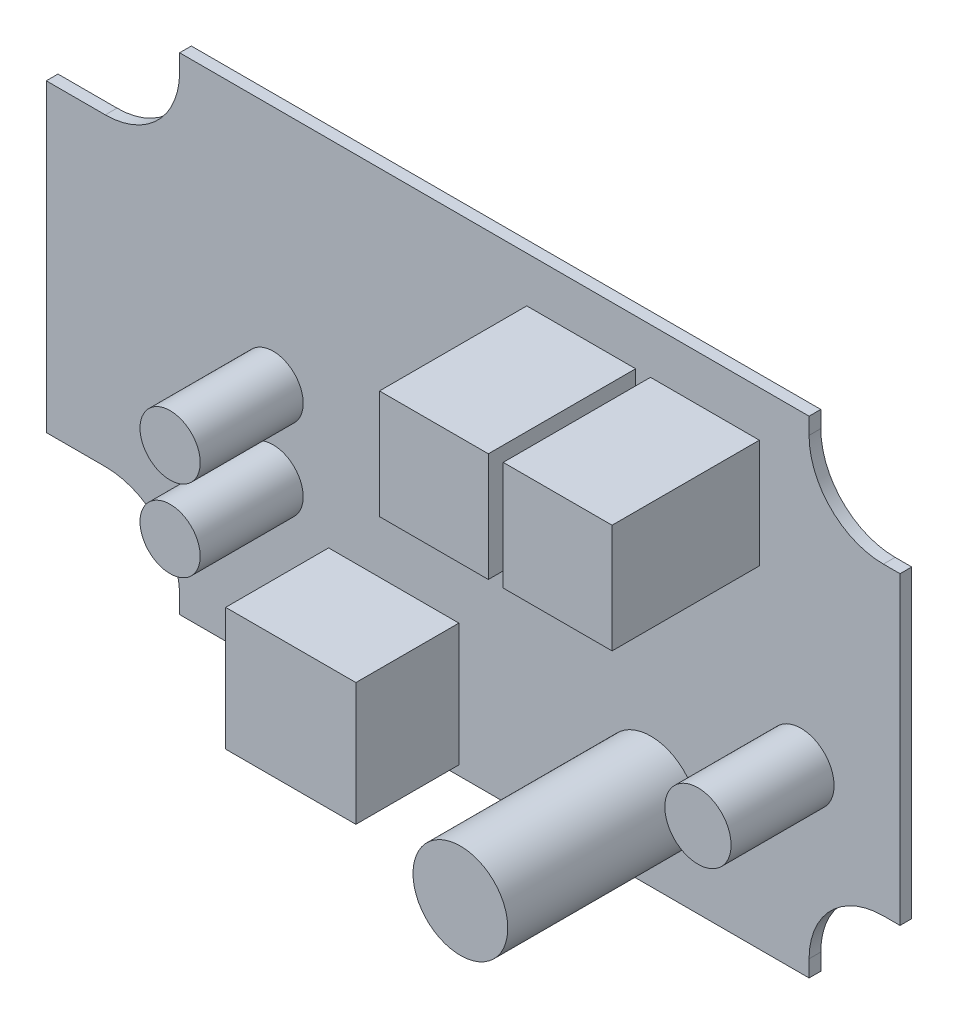
SolidWorks part; units mm, degrees
ref_plane "Front Plane" through (0, 0, 0) normal (0, 0, 1) x (1, 0, 0)
ref_plane "Top Plane" through (0, 0, 0) normal (0, 1, 0) x (1, 0, 0)
ref_plane "Right Plane" through (0, 0, 0) normal (1, 0, 0) x (0, 0, -1)
sketch "Sketch1" plane through (0, 0, 0) normal (0, 0, 1) x (1, 0, 0)
  line L0 (-42.3541, 30.2967) -> (-52.3541, 30.2967) construction
  line L1 (42.3541, -30.7033) -> (42.3541, -32.9433)
  line L2 (-52.3541, -20.7033) -> (-60.3013, -20.7033)
  line L4 (52.3541, -20.7033) -> (54.5933, -20.7033)
  line L5 (-52.3541, 30.2967) -> (-52.3541, 20.2967) construction
  line L6 (-52.3541, -20.7033) -> (-52.3541, -30.7033) construction
  line L7 (-52.3541, -30.7033) -> (-42.3541, -30.7033) construction
  line L8 (42.3541, -30.7033) -> (52.3541, -30.7033) construction
  line L9 (52.3541, -30.7033) -> (52.3541, -20.7033) construction
  line L10 (52.3541, 20.2967) -> (52.3541, 30.2967) construction
  line L11 (52.3541, 30.2967) -> (42.3541, 30.2967) construction
  line L12 (54.5933, -20.7033) -> (54.5933, 20.2967)
  line L13 (-60.3013, -20.7033) -> (-60.3013, 20.2967)
  line L14 (-60.3013, 20.2967) -> (-52.3541, 20.2967)
  line L15 (54.5933, 20.2967) -> (52.3541, 20.2967)
  line L16 (42.3541, -32.9433) -> (-42.3541, -32.9433)
  line L17 (-42.3541, -32.9433) -> (-42.3541, -30.7033)
  line L21 (0, -32.9433) -> (0, 0) construction
  line L24 (42.3541, 30.2967) -> (42.3541, 32.5367)
  line L25 (42.3541, 32.5367) -> (-42.3541, 32.5367)
  line L26 (-42.3541, 32.5367) -> (-42.3541, 30.2967)
  arc A0 (-42.3541, 30.2967) -> (-52.3541, 20.2967) centre (-52.3541, 30.2967) cw
  arc A2 (-52.3541, -20.7033) -> (-42.3541, -30.7033) centre (-52.3541, -30.7033) cw
  arc A4 (42.3541, 30.2967) -> (52.3541, 20.2967) centre (52.3541, 30.2967) ccw
  arc A5 (52.3541, -20.7033) -> (42.3541, -30.7033) centre (52.3541, -30.7033) ccw
  dimension "D1" = 41
  dimension "D3" = 10
  dimension "D5" = 84.7082
  dimension "D6" = 2.24
  dimension "D7" = 7.9472
  dimension "D8" = 2.2392
extrude "Boss-Extrude1" add sketch "Sketch1" along normal blind 1.5748
sketch "Sketch2" plane through (0, 0, 1.5748) normal (0, 0, 1) x (1, 0, 0)
  line L1 (4.3619, 26.3914) -> (19.0119, 26.3914)
  line L2 (4.3619, 26.3914) -> (4.3619, 11.7414)
  line L3 (4.3619, 11.7414) -> (19.0119, 11.7414)
  line L4 (19.0119, 26.3914) -> (19.0119, 11.7414)
  line L5 (21.0119, 26.3914) -> (35.6619, 26.3914)
  line L6 (21.0119, 26.3914) -> (21.0119, 11.7414)
  line L7 (21.0119, 11.7414) -> (35.6619, 11.7414)
  line L8 (35.6619, 26.3914) -> (35.6619, 11.7414)
  dimension "D1" = 2
  dimension "D2" = 14.65
extrude "Boss-Extrude2" add sketch "Sketch2" along normal blind 19.82
sketch "Sketch3" plane through (0, 0, 1.5748) normal (0, 0, 1) x (1, 0, 0)
  circle A0 centre (21.0509, -21.7791) radius 6.38
  dimension "D1" = 12.76
extrude "Boss-Extrude3" add sketch "Sketch3" along normal blind 25.62
sketch "Sketch4" plane through (0, 0, 1.5748) normal (0, 0, 1) x (1, 0, 0)
  line L1 (-22.3027, -15.1438) -> (-4.7739, -15.1438)
  line L2 (-22.3027, -15.1438) -> (-22.3027, -31.671)
  line L3 (-22.3027, -31.671) -> (-4.7739, -31.671)
  line L4 (-4.7739, -15.1438) -> (-4.7739, -31.671)
  circle A0 centre (-29.7754, 0) radius 4.05
  circle A1 centre (-29.7754, -10.91) radius 4.05
  circle A2 centre (41.2613, -8.8411) radius 4.4585
  dimension "D1" = 8.1
  dimension "D2" = 16.5272
  dimension "D4" = 8.9169
  dimension "D3" = 17.5288
extrude "Boss-Extrude4" add sketch "Sketch4" along normal blind 13.86
